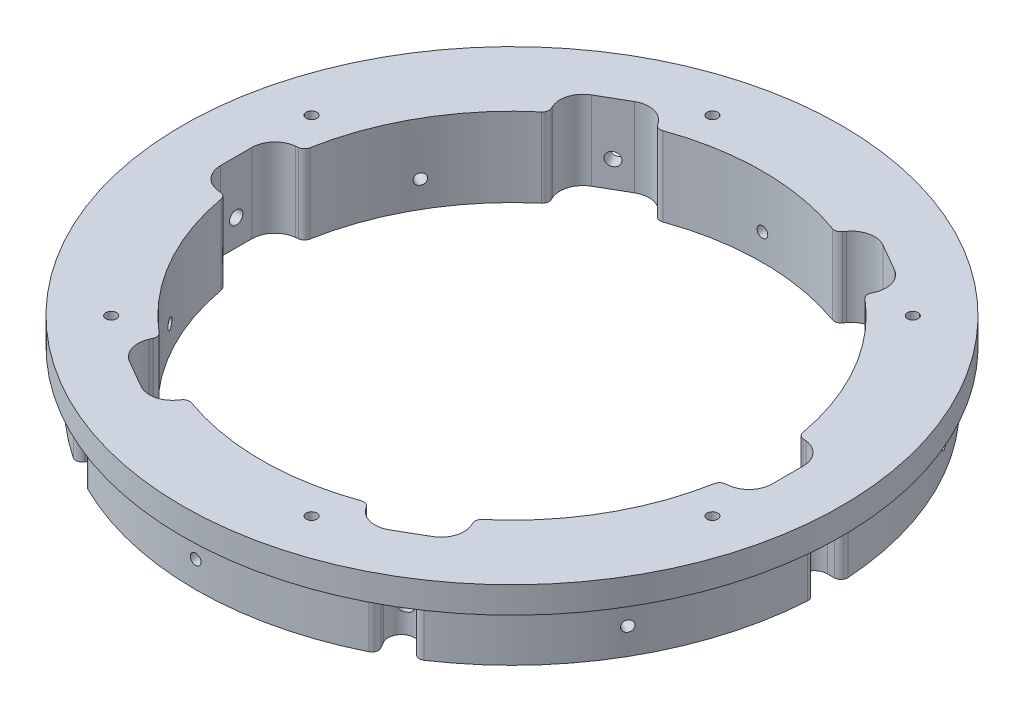
SolidWorks part; units mm, degrees
material "6061-T6 (SS)"
ref_plane "Front Plane" through (0, 0, 0) normal (0, 0, 1) x (1, 0, 0)
ref_plane "Top Plane" through (0, 0, 0) normal (0, 1, 0) x (1, 0, 0)
ref_plane "Right Plane" through (0, 0, 0) normal (1, 0, 0) x (0, 0, -1)
sketch "Sketch1" plane through (0, 0, 0) normal (0, 1, 0) x (1, 0, 0)
  circle A0 centre (0, 0) radius 76.2
  circle A1 centre (0, 0) radius 60.325
  dimension "D1" = 152.4
  dimension "D2" = 120.65
extrude "Boss-Extrude1" add sketch "Sketch1" against normal blind 19.05
sketch "Sketch3" plane through (0, -19.05, 0) normal (0, -1, 0) x (-1, 0, 0)
  line L0 (-76.1338, 3.175) -> (-72.771, 3.175)
  line L1 (-76.1338, -3.175) -> (-72.771, -3.175)
  circle A0 centre (0, 0) radius 76.2 construction
  arc A1 (-72.771, 3.175) -> (-72.771, -3.175) centre (-72.771, 0) cw
  arc A2 (-76.1338, -3.175) -> (-76.1338, 3.175) centre (0, 0) cw
  point P9 (-69.596, 0)
  point P13 (-76.2, 0)
  dimension "D1" = 6.35
  dimension "D2" = 6.604
extrude "Cut-Extrude1" cut sketch "Sketch3" against normal blind 12.7
sketch "Sketch4" plane through (0, -19.05, 0) normal (0, -1, 0) x (-1, 0, 0)
  line L0 (-66.421, 8.7312) -> (-66.421, -8.7312)
  line L1 (-66.421, -8.7312) -> (-59.5683, -9.525)
  line L2 (-59.5683, -9.525) -> (-59.5683, 9.525)
  line L3 (-59.5683, 9.525) -> (-66.421, 8.7312)
  line L4 (-66.421, 0) -> (0, 0) construction
  circle A0 centre (0, 0) radius 60.325 construction
  dimension "D1" = 3.175
  dimension "D2" = 19.05
  dimension "D3" = 17.4625
extrude "Cut-Extrude2" cut sketch "Sketch4" against normal through all
hole_wizard "1/8 (0.125) Diameter Hole1" positions "Sketch5" profile "Sketch6" hole size "1/8" standard "ANSI Inch" end condition through all
sketch "Sketch5" plane through (66.421, 0, 0) normal (-1, 0, 0) x (0, 0, 1)
  line L0 (-8.7312, -19.05) -> (8.7312, -19.05) construction
  point P0 (0, -12.7)
  dimension "D1" = 6.35
sketch "Sketch6" plane through (66.421, -12.7, 0) normal (0, 1, 0) x (0, 0, 1)
  line L0 (0, 0) -> (0, 9.779)
  line L1 (0, 9.779) -> (1.5875, 9.779)
  line L2 (1.5875, 9.779) -> (1.5875, 0)
  line L5 (1.5875, 0) -> (0, 0)
  line L11 (0, -6.35) -> (0, 107.95) construction
  dimension "Thru Hole Dia." = 3.175
  dimension "Thru Hole Depth" = 9.779
fillet "Fillet1" radius 1.5875 4 edges at (76.1338, -12.7, 3.175) (76.1338, -12.7, -3.175) (59.5683, -9.525, 9.525) (59.5683, -9.525, -9.525)
fillet "Fillet2" radius 5.5562 2 edges at (66.421, -9.525, 8.7312) (66.421, -9.525, -8.7312)
sketch "Sketch9" plane through (0, 0, 0) normal (0, 0, 1) x (1, 0, 0)
  line L0 (-76.2, -19.05) -> (76.0446, -19.05) construction
  circle A0 centre (0, -12.7) radius 1.2891
  dimension "D1" = 2.5781
  dimension "D2" = 6.35
extrude "Cut-Extrude3" cut sketch "Sketch9" against normal through all
sketch "Sketch11" plane through (0, -19.05, 0) normal (0, -1, 0) x (1, 0, 0)
  line L0 (0, 0) -> (76.2, 0) construction
  line L1 (0, 0) -> (65.9365, 17.6676) construction
  line L2 (58.2695, 15.6133) -> (73.6035, 19.722) construction
  circle A0 centre (65.9365, 17.6676) radius 1.289
  arc A1 (76.0446, -4.8638) -> (76.0446, 4.8638) centre (0, 0) ccw construction
  arc A2 (59.3714, 10.6838) -> (59.3714, -10.6838) centre (0, 0) ccw construction
  arc A3 (76.0446, 4.8638) -> (76.0446, -4.8638) centre (0, 0) ccw construction
  point P18 (65.9365, 17.6676)
  dimension "D1" = 2.5781
  dimension "D2" = 15
extrude "Cut-Extrude5" cut sketch "Sketch11" against normal through all
pattern_circular "CirPattern1" count 6 over 360 about axis through (0, -19.05, 0) along (0, 1, 0) of "Cut-Extrude1", "Cut-Extrude2", "Fillet2", "Fillet1", "1/8 (0.125) Diameter Hole1", "Cut-Extrude3", "Cut-Extrude5"
sketch "Sketch8" plane through (0, 0, 0) normal (0, 1, 0) x (1, 0, 0)
  circle A0 centre (0, 0) radius 79.375
  circle A1 centre (0, 0) radius 76.2
  circle A2 centre (0, 0) radius 76.2 construction
  dimension "D1" = 3.175
extrude "Boss-Extrude3" add sketch "Sketch8" against normal up to surface (6.35 mm away) up to face at (-74.0439, -6.35, 0)
